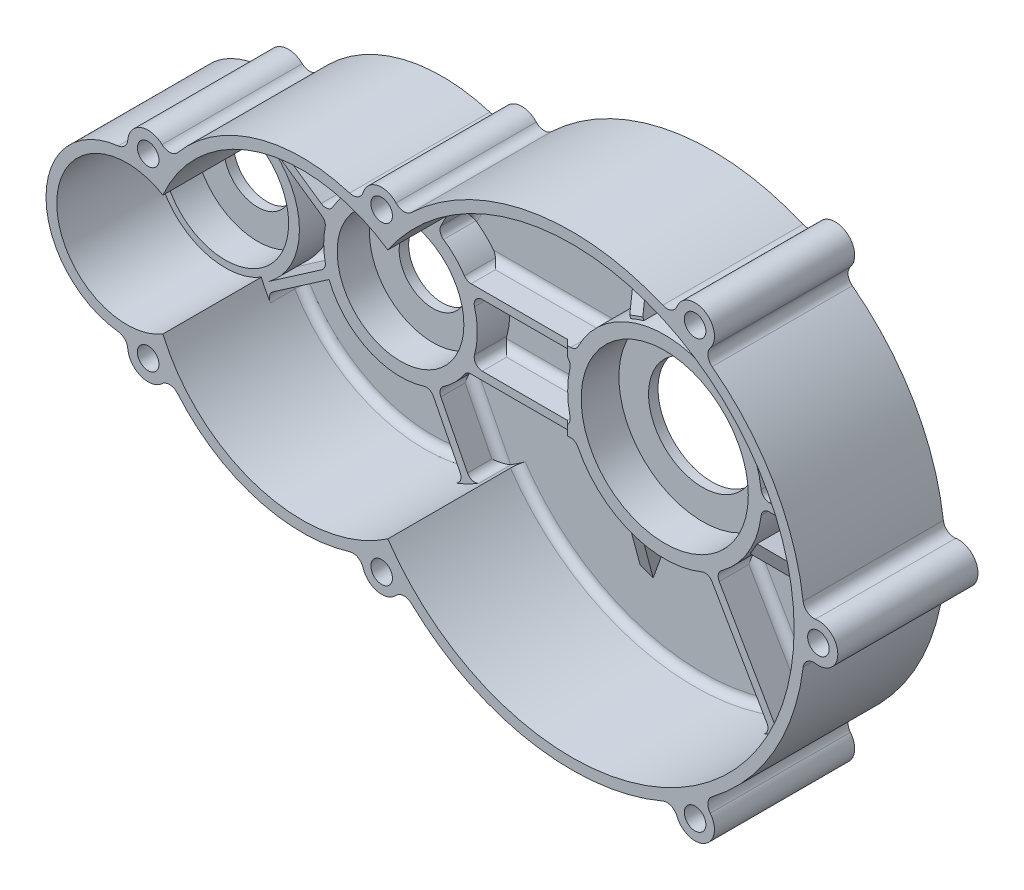
SolidWorks part; units mm, degrees
material "6061-T6 (SS)"
ref_plane "Front Plane" through (0, 0, 0) normal (0, 0, 1) x (1, 0, 0)
ref_plane "Top Plane" through (0, 0, 0) normal (0, 1, 0) x (1, 0, 0)
ref_plane "Right Plane" through (0, 0, 0) normal (1, 0, 0) x (0, 0, -1)
sketch "Sketch1" plane through (0, 0, 0) normal (0, 0, 1) x (1, 0, 0)
  line L0 (8.75, 0) -> (427.2506, 0) construction
  arc A0 (11.4995, -27.7085) -> (95.7391, -51.8187) centre (65, 0) ccw
  arc A1 (11.4995, 27.7085) -> (11.4995, -27.7085) centre (0, 0) ccw
  arc A2 (95.7391, -51.8187) -> (95.7391, 51.8187) centre (165, 0) ccw
  arc A3 (95.7391, 51.8187) -> (11.4995, 27.7085) centre (65, 0) ccw
  arc A5 (96.7891, 46.406) -> (13.3611, 22.3043) centre (65, 0) ccw
  arc A7 (13.3611, 22.3043) -> (13.3611, -22.3043) centre (0, 0) ccw
  arc A8 (13.3611, -22.3043) -> (96.7891, -46.406) centre (65, 0) ccw
  arc A12 (96.7891, -46.406) -> (96.7891, 46.406) centre (165, 0) ccw
  arc A13 (96.7891, 46.406) -> (12.5, 20.1944) centre (65, 0) ccw construction
  arc A14 (12.5, -20.1944) -> (96.7891, -46.406) centre (65, 0) ccw construction
  arc A15 (12.5, 20.1944) -> (12.5, -20.1944) centre (0, 0) ccw construction
  arc A16 (10.5, 25.6868) -> (10.5, -25.6868) centre (0, 0) ccw construction
  arc A17 (95.7391, 51.8187) -> (10.5, 25.6868) centre (65, 0) ccw construction
  arc A18 (10.5, -25.6868) -> (95.7391, -51.8187) centre (65, 0) ccw construction
extrude "wall" add sketch "Sketch1" along normal blind 48.5
sketch "Sketch2" plane through (0, 0, 0) normal (0, 0, 1) x (1, 0, 0)
  arc A3 (95.7391, -51.8187) -> (95.7391, 51.8187) centre (165, 0) ccw construction
  arc A4 (11.4995, 27.7085) -> (11.4995, -27.7085) centre (0, 0) ccw
  arc A5 (95.7391, 51.8187) -> (11.4995, 27.7085) centre (65, 0) ccw
  arc A6 (11.4995, -27.7085) -> (95.7391, -51.8187) centre (65, 0) ccw construction
  arc A7 (95.7391, -51.8187) -> (95.7391, 51.8187) centre (165, 0) ccw
  arc A8 (11.4995, -27.7085) -> (95.7391, -51.8187) centre (65, 0) ccw
extrude "plate" add sketch "Sketch2" against normal blind 5
sketch "Sketch3" plane through (0, 0, 0) normal (0, 0, 1) x (1, 0, 0)
  circle A0 centre (0, 0) radius 12.5
  circle A1 centre (165, 0) radius 20
  arc A2 (96.7891, -46.406) -> (96.7891, 46.406) centre (165, 0) ccw construction
  circle A3 centre (65, 0) radius 12.5
  dimension "D1" = 25
  dimension "D2" = 25
  dimension "D3" = 40
extrude "shaft holes" cut sketch "Sketch3" against normal up to surface (5 mm away) up to face at (79.5858, 0, -5)
sketch "Sketch5" plane through (0, 0, 48.5) normal (0, 0, 1) x (1, 0, 0)
  line L0 (-59.8844, 0) -> (275.5983, 0) construction
  line L1 (10.5, 25.6868) -> (9.2682, 29.0695)
  circle A0 centre (7.8996, 32.8281) radius 4
  circle A1 centre (7.8996, 32.8281) radius 7.6
  circle A2 centre (94.5038, 58.1864) radius 4
  circle A3 centre (94.5038, 58.1864) radius 7.2
  circle A4 centre (210.75, 79.2413) radius 4
  circle A5 centre (210.75, 79.2413) radius 7.2
  circle A6 centre (210.75, -79.2413) radius 7.2
  circle A7 centre (210.75, -79.2413) radius 4
  circle A8 centre (94.5038, -58.1864) radius 7.2
  circle A9 centre (94.5038, -58.1864) radius 4
  circle A10 centre (7.8996, -32.8281) radius 4
  circle A11 centre (7.8996, -32.8281) radius 7.6
  circle A12 centre (165, 0) radius 91.5 construction
  circle A13 centre (256.5, 0) radius 4
  circle A14 centre (256.5, 0) radius 7.2
  point P23 (256.5, 0)
extrude "mount holes" add sketch "Sketch5" against normal up to surface (53.5 mm away)
sketch "Sketch6" plane through (0, 0, 0) normal (0, 0, 1) x (1, 0, 0)
  line L0 (-43.2888, 0) -> (284.0105, 0) construction
  line L1 (36.8297, 7.9818) -> (37.5081, 7.5131)
  line L2 (15.3611, 26.4583) -> (38.5348, 10.4501)
  line L3 (38.5348, 10.4501) -> (38.4957, 10.4771)
  line L4 (200.9687, -1.5) -> (247.4614, -1.5)
  line L5 (88.5726, 51.0724) -> (76.0061, 26.2891)
  line L6 (91.2621, 49.743) -> (78.7091, 24.9862)
  line L7 (91.0728, 11.5091) -> (130.8893, 11.5091)
  line L8 (207.544, -71.8027) -> (183.8104, -30.6948)
  line L9 (204.9555, -73.3193) -> (181.1891, -32.1545)
  line L10 (89.5303, 14.5091) -> (132.0533, 14.5091)
  line L11 (91.0728, -11.5091) -> (130.8893, -11.5091)
  line L12 (89.5303, -14.5091) -> (132.0533, -14.5091)
  line L13 (91.2621, -49.743) -> (78.7091, -24.9862)
  line L14 (204.9555, 73.3193) -> (181.1891, 32.1545)
  line L15 (207.544, 71.8027) -> (183.8104, 30.6948)
  line L16 (88.5726, -51.0724) -> (76.0061, -26.2891)
  line L17 (15.6301, -22.6263) -> (36.8297, -7.9818)
  line L18 (15.3611, -26.4583) -> (38.5348, -10.4501)
  line L19 (36.8297, -7.9818) -> (37.5081, -7.5131)
  line L20 (200.9687, 1.5) -> (247.4614, 1.5)
  line L21 (15.6301, 22.6263) -> (36.8297, 7.9818)
  line L22 (38.5348, 10.4501) -> (48.6972, 3.43) construction
  line L23 (6.1722, 29.1597) -> (36.8297, 7.9818) construction
  line L24 (36.8297, 7.9818) -> (46.9921, 0.9616) construction
  line L25 (7.8774, 31.6281) -> (38.5348, 10.4501) construction
  line L26 (38.5348, -10.4501) -> (38.4957, -10.4771)
  line L27 (204.9555, 73.3193) -> (206.0662, 75.2431)
  line L28 (206.0662, 75.2431) -> (208.6643, 73.7431)
  line L29 (208.6643, 73.7431) -> (207.544, 71.8027)
  line L30 (207.544, -71.8027) -> (208.6643, -73.7431)
  line L31 (208.6643, -73.7431) -> (206.0662, -75.2431)
  line L32 (206.0662, -75.2431) -> (204.9555, -73.3193)
  line L33 (247.4614, 1.5) -> (249.235, 1.5)
  line L34 (249.235, 1.5) -> (249.235, -1.5)
  line L35 (249.235, -1.5) -> (247.4614, -1.5)
  line L36 (215.4442, -32.5883) -> (194.6666, -20.3935)
  line L37 (218.0474, -28.1529) -> (197.2698, -15.9582)
  line L38 (144.2218, 57.3494) -> (146.7076, 58.2468)
  line L39 (216.7096, -30.4322) -> (218.0474, -28.1529)
  line L40 (216.7096, -30.4322) -> (215.4442, -32.5883)
  line L41 (146.7076, -58.2468) -> (155.2265, -34.6479)
  line L42 (141.8703, -56.5006) -> (150.3891, -32.9017)
  line L43 (144.2218, 57.3494) -> (141.8703, 56.5006)
  line L44 (141.8703, 56.5006) -> (150.3891, 32.9017)
  line L45 (146.7076, 58.2468) -> (155.2265, 34.6479)
  line L46 (216.7096, 30.4322) -> (215.4442, 32.5883)
  line L47 (216.7096, 30.4322) -> (218.0474, 28.1529)
  line L48 (215.4442, 32.5883) -> (194.6666, 20.3935)
  line L49 (218.0474, 28.1529) -> (197.2698, 15.9582)
  line L50 (144.2218, -57.3494) -> (141.8703, -56.5006)
  line L51 (144.2218, -57.3494) -> (146.7076, -58.2468)
  circle A0 centre (65, 0) radius 23.5
  arc A1 (37.5081, 7.5131) -> (37.5081, -7.5131) centre (65, 0) ccw
  arc A2 (12.4091, -19.9565) -> (12.4091, 19.9565) centre (0, 0) ccw
  arc A3 (132.0533, -14.5091) -> (150.3891, -32.9017) centre (165, 0) ccw
  arc A4 (150.3891, 32.9017) -> (132.0533, 14.5091) centre (165, 0) ccw
  arc A5 (13.3611, -22.3043) -> (13.9784, -23.6824) centre (65, 0) ccw
  arc A6 (13.9784, 23.6824) -> (13.3611, 22.3043) centre (65, 0) ccw
  arc A7 (15.3611, 26.4583) -> (13.3611, 22.3043) centre (65, 0) ccw
  arc A8 (15.6301, 22.6263) -> (15.6301, -22.6263) centre (0, 0) cw
  arc A9 (181.1891, 32.1545) -> (155.2265, 34.6479) centre (165, 0) ccw
  arc A10 (13.3611, -22.3043) -> (13.9784, -23.6824) centre (65, 0) ccw
  circle A11 centre (165, 0) radius 31
  arc A12 (91.2621, 49.743) -> (88.5726, 51.0724) centre (65, 0) ccw
  arc A13 (76.0061, 26.2891) -> (38.4957, 10.4771) centre (65, 0) ccw
  arc A14 (89.5303, 14.5091) -> (78.7091, 24.9862) centre (65, 0) ccw
  arc A15 (194.6666, 20.3935) -> (183.8104, 30.6948) centre (165, 0) ccw
  arc A16 (155.2265, -34.6479) -> (181.1891, -32.1545) centre (165, 0) ccw
  arc A17 (91.2621, -49.743) -> (88.5726, -51.0724) centre (65, 0) cw
  arc A18 (15.3611, -26.4583) -> (13.3611, -22.3043) centre (65, 0) cw
  arc A19 (13.9784, -23.6824) -> (13.3611, -22.3043) centre (65, 0) cw
  arc A20 (38.4957, -10.4771) -> (76.0061, -26.2891) centre (65, 0) ccw
  arc A21 (91.0728, -11.5091) -> (91.0728, 11.5091) centre (65, 0) ccw
  arc A22 (78.7091, -24.9862) -> (89.5303, -14.5091) centre (65, 0) ccw
  arc A23 (183.8104, -30.6948) -> (194.6666, -20.3935) centre (165, 0) ccw
  arc A24 (200.9687, 1.5) -> (197.2698, 15.9582) centre (165, 0) ccw
  arc A25 (130.8893, 11.5091) -> (130.8893, -11.5091) centre (165, 0) ccw
  arc A26 (12.4091, 19.9565) -> (14.426, -18.551) centre (0, 0) ccw
  arc A27 (13.3611, 22.3043) -> (13.3611, -22.3043) centre (0, 0) ccw
  arc A28 (197.2698, -15.9582) -> (200.9687, -1.5) centre (165, 0) ccw
  dimension "D1" = 3
  dimension "D2" = 3
  dimension "D6" = 5
  dimension "D7" = 5
  dimension "D8" = 5
  dimension "D3" = 3
  dimension "D4" = 3
  dimension "D5" = 3
  dimension "D10" = 90
extrude "Stiffners" add sketch "Sketch6" along normal blind 12
fillet "3mm fillet" radius 3 56 edges at (110.981, -11.5091, 0) (110.981, 11.5091, 0) (26.5691, 15.0697, 0) (26.5691, -15.0697, 0) (82.2894, -38.6808, 0) (192.8223, -52.304, 0) (145.6007, -80.1868, 0) (84.9856, -37.3646, 0) (224.2275, -1.5, 0) (236.3074, -41.491, 0) (195.4371, -50.8329, 0) (195.4371, 50.8329, 0) (236.3074, 41.491, 0) (224.2275, 1.5, 0) (84.9856, 37.3646, 0) (145.6007, 80.1868, 0) (192.8223, 52.304, 0) (26.9284, 18.4677, 0) (47.0744, 53.3173, 0) (82.2894, 38.6808, 0) (91.0728, -11.5091, 6) (91.0728, 11.5091, 6) (130.8893, 11.5091, 6) (130.8893, -11.5091, 6) (247.4864, 1.5, 6) (247.4864, -1.5, 6) (207.0638, 70.971, 6) (204.4556, 72.4535, 6) (181.1891, 32.1545, 6) (200.9687, 1.5, 6) (183.8104, -30.6948, 6) (207.0638, -70.971, 6) (204.4556, -72.4535, 6) (78.7091, -24.9862, 6) (76.0061, -26.2891, 6) (15.3611, 26.4583, 6) (88.5726, 51.0724, 6) (91.2621, 49.743, 6) (76.0061, 26.2891, 6) (78.7091, 24.9862, 6) (37.5081, -7.5131, 6) (37.5081, 7.5131, 6) (38.4957, 10.4771, 6) (88.5726, -51.0724, 6) (91.2621, -49.743, 6) (110.7918, 14.5091, 0) (110.7918, -14.5091, 0) (89.5303, -14.5091, 6) (89.5303, 14.5091, 6) (132.0533, -14.5091, 6) (47.0744, -53.3173, 0) (200.9687, -1.5, 6) (181.1891, -32.1545, 6) (26.9284, -18.4677, 0) (15.3611, -26.4583, 6) (183.8104, 30.6948, 6)
sketch "Sketch9" plane through (0, 0, 0) normal (0, 0, 1) x (1, 0, 0)
  circle A0 centre (165, 0) radius 20 construction
  circle A1 centre (165, 0) radius 31 construction
  circle A2 centre (165, 0) radius 31
  circle A3 centre (165, 0) radius 20
extrude "output bearing width" cut sketch "Sketch9" against normal blind 2
fillet "4mm fillet" radius 4 14 edges at (101.6667, -58.9164, 21.75) (203.8162, -77.3017, 21.75) (212.5372, -72.2667, 21.75) (101.6667, 58.9164, 21.75) (203.8162, 77.3017, 21.75) (212.5372, 72.2667, 21.75) (251.3533, 5.0351, 21.75) (251.3533, -5.0351, 21.75) (15.3795, -34.174, 21.75) (87.7084, -55.8067, 21.75) (0.8502, -29.9879, 21.75) (15.3795, 34.174, 21.75) (0.8502, 29.9879, 21.75) (87.7084, 55.8067, 21.75)
sketch "Sketch10" plane through (0, 0, -5) normal (0, 0, -1) x (-1, 0, 0)
  arc A28 (-82.6177, -57.6167) -> (-18.8634, -38.7489) centre (-65, 0) ccw
  arc A29 (-13.076, -38.3927) -> (-18.8634, -38.7489) centre (-15.8004, -41.3215) ccw
  arc A30 (-13.076, -38.3927) -> (-0.3265, -33.4665) centre (-7.8996, -32.8281) ccw
  arc A31 (3.2289, -29.8257) -> (-0.3265, -33.4665) centre (3.6594, -33.8025) ccw
  arc A32 (3.2289, -29.8257) -> (3.2289, 29.8257) centre (0, 0) ccw
  arc A33 (-0.3265, 33.4665) -> (3.2289, 29.8257) centre (3.6594, 33.8025) ccw
  arc A34 (-0.3265, 33.4665) -> (-13.076, 38.3927) centre (-7.8996, 32.8281) ccw
  arc A35 (-18.8634, 38.7489) -> (-13.076, 38.3927) centre (-15.8004, 41.3215) ccw
  arc A36 (-18.8634, 38.7489) -> (-82.6177, 57.6167) centre (-65, 0) ccw
  arc A37 (-87.6146, 60.2792) -> (-82.6177, 57.6167) centre (-83.7873, 61.4418) ccw
  arc A38 (-87.6146, 60.2792) -> (-99.8286, 63.0326) centre (-94.5038, 58.1864) ccw
  arc A39 (-105.5366, 62.82) -> (-99.8286, 63.0326) centre (-102.7869, 65.725) ccw
  arc A40 (-105.5366, 62.82) -> (-198.7591, 79.6403) centre (-165, 0) ccw
  arc A41 (-204.0452, 81.8653) -> (-198.7591, 79.6403) centre (-200.3203, 83.323) ccw
  arc A42 (-204.0452, 81.8653) -> (-216.3748, 74.7467) centre (-210.75, 79.2413) ccw
  arc A43 (-217.0909, 69.0564) -> (-216.3748, 74.7467) centre (-219.4997, 72.2498) ccw
  arc A44 (-217.0909, 69.0564) -> (-250.8501, 10.5839) centre (-165, 0) ccw
  arc A45 (-255.42, 7.1185) -> (-250.8501, 10.5839) centre (-254.82, 11.0733) ccw
  arc A46 (-255.42, 7.1185) -> (-255.42, -7.1185) centre (-256.5, 0) ccw
  arc A47 (-250.8501, -10.5839) -> (-255.42, -7.1185) centre (-254.82, -11.0733) ccw
  arc A48 (-250.8501, -10.5839) -> (-217.0909, -69.0564) centre (-165, 0) ccw
  arc A49 (-216.3748, -74.7467) -> (-217.0909, -69.0564) centre (-219.4997, -72.2498) ccw
  arc A50 (-216.3748, -74.7467) -> (-204.0452, -81.8653) centre (-210.75, -79.2413) ccw
  arc A51 (-198.7591, -79.6403) -> (-204.0452, -81.8653) centre (-200.3203, -83.323) ccw
  arc A52 (-198.7591, -79.6403) -> (-105.5366, -62.82) centre (-165, 0) ccw
  arc A53 (-99.8286, -63.0326) -> (-105.5366, -62.82) centre (-102.7869, -65.725) ccw
  arc A54 (-99.8286, -63.0326) -> (-87.6146, -60.2792) centre (-94.5038, -58.1864) ccw
  arc A55 (-82.6177, -57.6167) -> (-87.6146, -60.2792) centre (-83.7873, -61.4418) ccw
  arc A56 (-82.6177, -57.6167) -> (-18.8634, -38.7489) centre (-65, 0) ccw
  arc A57 (-13.076, -38.3927) -> (-18.8634, -38.7489) centre (-15.8004, -41.3215) ccw
  arc A58 (-13.076, -38.3927) -> (-0.3265, -33.4665) centre (-7.8996, -32.8281) ccw
  arc A59 (3.2289, -29.8257) -> (-0.3265, -33.4665) centre (3.6594, -33.8025) ccw
  arc A60 (3.2289, -29.8257) -> (3.2289, 29.8257) centre (0, 0) ccw
  arc A61 (-0.3265, 33.4665) -> (3.2289, 29.8257) centre (3.6594, 33.8025) ccw
  arc A62 (-0.3265, 33.4665) -> (-13.076, 38.3927) centre (-7.8996, 32.8281) ccw
  arc A63 (-18.8634, 38.7489) -> (-13.076, 38.3927) centre (-15.8004, 41.3215) ccw
  arc A64 (-18.8634, 38.7489) -> (-82.6177, 57.6167) centre (-65, 0) ccw
  arc A65 (-87.6146, 60.2792) -> (-82.6177, 57.6167) centre (-83.7873, 61.4418) ccw
  arc A66 (-87.6146, 60.2792) -> (-99.8286, 63.0326) centre (-94.5038, 58.1864) ccw
  arc A67 (-105.5366, 62.82) -> (-99.8286, 63.0326) centre (-102.7869, 65.725) ccw
  arc A68 (-105.5366, 62.82) -> (-198.7591, 79.6403) centre (-165, 0) ccw
  arc A69 (-204.0452, 81.8653) -> (-198.7591, 79.6403) centre (-200.3203, 83.323) ccw
  arc A70 (-204.0452, 81.8653) -> (-216.3748, 74.7467) centre (-210.75, 79.2413) ccw
  arc A71 (-217.0909, 69.0564) -> (-216.3748, 74.7467) centre (-219.4997, 72.2498) ccw
  arc A72 (-217.0909, 69.0564) -> (-250.8501, 10.5839) centre (-165, 0) ccw
  arc A73 (-255.42, 7.1185) -> (-250.8501, 10.5839) centre (-254.82, 11.0733) ccw
  arc A74 (-255.42, 7.1185) -> (-255.42, -7.1185) centre (-256.5, 0) ccw
  arc A75 (-250.8501, -10.5839) -> (-255.42, -7.1185) centre (-254.82, -11.0733) ccw
  arc A76 (-250.8501, -10.5839) -> (-217.0909, -69.0564) centre (-165, 0) ccw
  arc A77 (-216.3748, -74.7467) -> (-217.0909, -69.0564) centre (-219.4997, -72.2498) ccw
  arc A78 (-216.3748, -74.7467) -> (-204.0452, -81.8653) centre (-210.75, -79.2413) ccw
  arc A79 (-198.7591, -79.6403) -> (-204.0452, -81.8653) centre (-200.3203, -83.323) ccw
  arc A80 (-198.7591, -79.6403) -> (-105.5366, -62.82) centre (-165, 0) ccw
  arc A81 (-99.8286, -63.0326) -> (-105.5366, -62.82) centre (-102.7869, -65.725) ccw
  arc A82 (-99.8286, -63.0326) -> (-87.6146, -60.2792) centre (-94.5038, -58.1864) ccw
  arc A83 (-82.6177, -57.6167) -> (-87.6146, -60.2792) centre (-83.7873, -61.4418) ccw
  dimension "D1" = 0
extrude "Cut-Extrude2" cut sketch "Sketch10" against normal blind 1.5
fillet "Fillet1" radius 3 1 edges at (132.0533, 14.5091, 7.5)
sketch "Sketch12" plane through (0, 0, 48.5) normal (0, 0, 1) x (1, 0, 0)
  circle A0 centre (7.8996, 32.8281) radius 4
  circle A1 centre (7.8996, 32.8281) radius 5.4506
extrude "Boss-Extrude1" add sketch "Sketch12" against normal up to surface (52 mm away) up to face at (-12.5, 0, -3.5)
sketch "Sketch13" plane through (0, 0, 48.5) normal (0, 0, 1) x (1, 0, 0)
  circle A0 centre (7.8996, 32.8281) radius 4
  circle A1 centre (7.8996, -32.8281) radius 4
  arc A2 (5.7752, -29.4389) -> (8.2496, -28.8434) centre (7.8996, -32.8281) ccw construction
extrude "Cut-Extrude4" cut sketch "Sketch13" against normal up to surface (52 mm away)
sketch "Sketch15" plane through (0, 0, -2) normal (0, 0, 1) x (1, 0, 0)
  circle A0 centre (165, 0) radius 20 construction
  circle A1 centre (165, 0) radius 31
  circle A2 centre (165, 0) radius 31
  circle A3 centre (165, 0) radius 20
  dimension "D1" = 0
extrude "Boss-Extrude3" add sketch "Sketch15" along normal blind 2
chamfer "Chamfer1" distance 24 distance2 12 4 edges at (144.289, -57.3737, 12) (144.289, 57.3737, 12) (216.7458, 30.3706, 12) (216.7458, -30.3706, 12)
sketch "Sketch18" plane through (0, 0, 12) normal (0, 0, 1) x (1, 0, 0)
  line L0 (203.7395, 1.5) -> (244.3725, 1.5) construction
  line L1 (203.7395, -1.5) -> (244.3725, -1.5) construction
  line L2 (202.888, -69.7382) -> (182.5538, -34.5184) construction
  line L3 (205.5176, -68.2929) -> (185.2166, -33.1305) construction
  line L4 (91.1855, 14.5091) -> (130.1513, 14.5091) construction
  line L7 (91.1855, -14.5091) -> (130.1513, -14.5091) construction
  line L8 (205.5176, 68.2929) -> (185.2166, 33.1305) construction
  line L9 (202.888, 69.7382) -> (182.5538, 34.5184) construction
  line L10 (203.7395, 1.5) -> (244.3725, 1.5)
  line L11 (203.7395, -1.5) -> (244.3725, -1.5)
  line L12 (202.888, -69.7382) -> (182.5538, -34.5184)
  line L13 (205.5176, -68.2929) -> (185.2166, -33.1305)
  line L14 (126.9396, 14.5091) -> (130.1513, 14.5091)
  line L15 (126.9396, -11.5091) -> (126.9396, -14.5091)
  line L17 (126.9396, -14.5091) -> (130.1513, -14.5091)
  line L18 (205.5176, 68.2929) -> (185.2166, 33.1305)
  line L19 (202.888, 69.7382) -> (182.5538, 34.5184)
  line L20 (126.9396, 14.5091) -> (126.9396, 11.5091)
  arc A0 (247.3677, -4.6698) -> (247.3677, 4.6698) centre (165, 0) ccw construction
  arc A1 (244.3725, 1.5) -> (247.3677, 4.6698) centre (244.3725, 4.5) ccw construction
  arc A2 (247.3677, -4.6698) -> (244.3725, -1.5) centre (244.3725, -4.5) ccw construction
  arc A3 (203.7395, -1.5) -> (200.7596, -4.1538) centre (203.7395, -4.5) ccw construction
  arc A4 (200.7596, 4.1538) -> (203.7395, 1.5) centre (203.7395, 4.5) ccw construction
  arc A5 (182.5538, -34.5184) -> (178.8053, -33.2478) centre (179.9558, -36.0184) ccw construction
  arc A6 (186.0597, -29.1974) -> (185.2166, -33.1305) centre (187.8147, -31.6305) ccw construction
  arc A7 (201.6216, -73.9264) -> (202.888, -69.7382) centre (200.2899, -71.2382) ccw construction
  arc A8 (205.5176, -68.2929) -> (209.7427, -69.3133) centre (208.1157, -66.7929) ccw construction
  arc A9 (201.6216, -73.9264) -> (209.7427, -69.3133) centre (165, 0) ccw construction
  arc A11 (130.1513, 14.5091) -> (132.832, 16.1622) centre (130.1513, 17.5091) ccw construction
  arc A13 (132.832, -16.1622) -> (130.1513, -14.5091) centre (130.1513, -17.5091) ccw construction
  arc A14 (185.2166, 33.1305) -> (186.0597, 29.1974) centre (187.8147, 31.6305) ccw construction
  arc A15 (178.8053, 33.2478) -> (182.5538, 34.5184) centre (179.9558, 36.0184) ccw construction
  arc A16 (202.888, 69.7382) -> (201.6216, 73.9264) centre (200.2899, 71.2382) ccw construction
  arc A17 (209.7427, 69.3133) -> (201.6216, 73.9264) centre (165, 0) ccw construction
  arc A18 (209.7427, 69.3133) -> (205.5176, 68.2929) centre (208.1157, 66.7929) ccw construction
  circle A19 centre (165, 0) radius 31 construction
  arc A20 (247.3677, -4.6698) -> (247.3677, 4.6698) centre (165, 0) ccw
  arc A21 (244.3725, 1.5) -> (247.3677, 4.6698) centre (244.3725, 4.5) ccw
  arc A22 (247.3677, -4.6698) -> (244.3725, -1.5) centre (244.3725, -4.5) ccw
  arc A23 (203.7395, -1.5) -> (200.7596, -4.1538) centre (203.7395, -4.5) ccw
  arc A24 (200.7596, 4.1538) -> (203.7395, 1.5) centre (203.7395, 4.5) ccw
  arc A25 (182.5538, -34.5184) -> (178.8053, -33.2478) centre (179.9558, -36.0184) ccw
  arc A26 (186.0597, -29.1974) -> (185.2166, -33.1305) centre (187.8147, -31.6305) ccw
  arc A27 (201.6216, -73.9264) -> (202.888, -69.7382) centre (200.2899, -71.2382) ccw
  arc A28 (205.5176, -68.2929) -> (209.7427, -69.3133) centre (208.1157, -66.7929) ccw
  arc A29 (201.6216, -73.9264) -> (209.7427, -69.3133) centre (165, 0) ccw
  arc A30 (129.8673, 7.8545) -> (126.9396, 11.5091) centre (126.9396, 8.5091) ccw construction
  arc A31 (130.1513, 14.5091) -> (132.832, 16.1622) centre (130.1513, 17.5091) ccw
  arc A32 (126.9396, -11.5091) -> (129.8673, -7.8545) centre (126.9396, -8.5091) ccw construction
  arc A33 (132.832, -16.1622) -> (130.1513, -14.5091) centre (130.1513, -17.5091) ccw
  arc A34 (185.2166, 33.1305) -> (186.0597, 29.1974) centre (187.8147, 31.6305) ccw
  arc A35 (178.8053, 33.2478) -> (182.5538, 34.5184) centre (179.9558, 36.0184) ccw
  arc A36 (202.888, 69.7382) -> (201.6216, 73.9264) centre (200.2899, 71.2382) ccw
  arc A37 (209.7427, 69.3133) -> (201.6216, 73.9264) centre (165, 0) ccw
  arc A38 (209.7427, 69.3133) -> (205.5176, 68.2929) centre (208.1157, 66.7929) ccw
  circle A39 centre (165, 0) radius 31
  arc A40 (178.8053, 33.2478) -> (132.832, 16.1622) centre (165, 0) ccw
  arc A41 (200.7596, 4.1538) -> (186.0597, 29.1974) centre (165, 0) ccw
  arc A42 (186.0597, -29.1974) -> (200.7596, -4.1538) centre (165, 0) ccw
  arc A43 (132.832, -16.1622) -> (178.8053, -33.2478) centre (165, 0) ccw
  arc A44 (129.8673, 7.8545) -> (129.8673, -7.8545) centre (165, 0) ccw construction
  arc A45 (129.8673, 7.8545) -> (126.9396, 11.5091) centre (126.9396, 8.5091) ccw
  arc A46 (126.9396, -11.5091) -> (129.8673, -7.8545) centre (126.9396, -8.5091) ccw
  arc A47 (129.8673, 7.8545) -> (129.8673, -7.8545) centre (165, 0) ccw
extrude "Boss-Extrude4" add sketch "Sketch18" along normal blind 2
chamfer "Chamfer2" distance 2 angle 45 2 edges at (126.9396, 13.0091, 14) (126.9396, -13.0091, 14)
